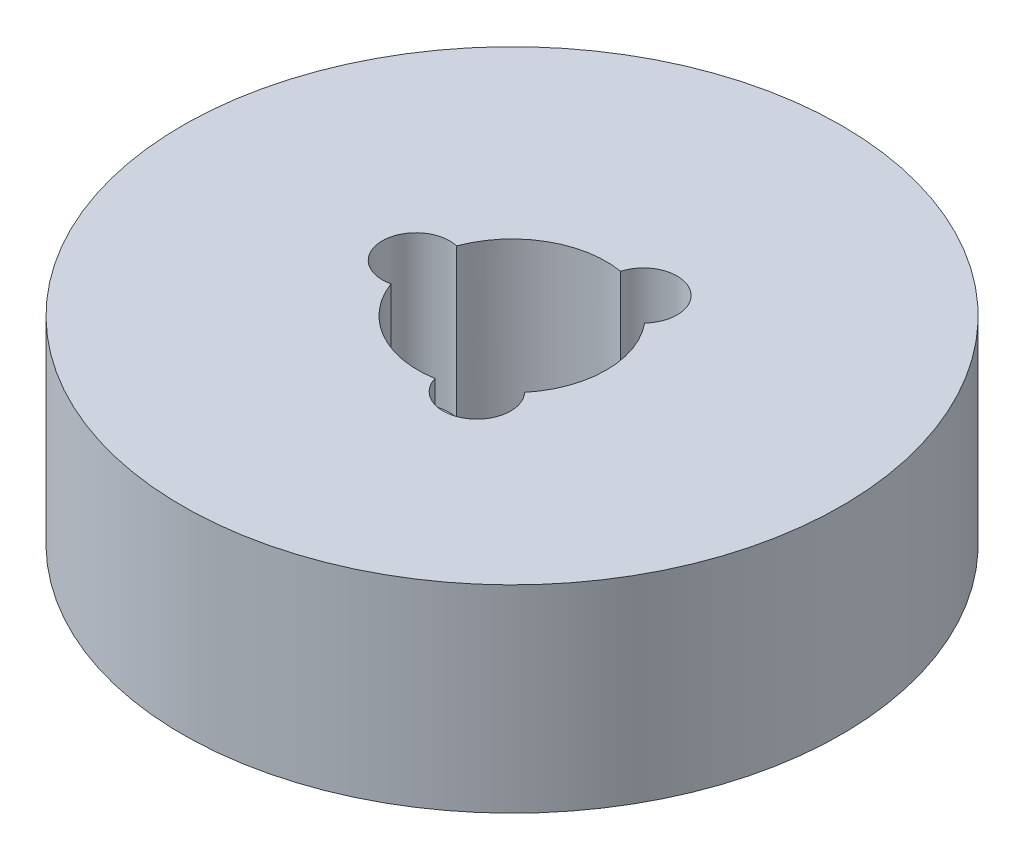
SolidWorks part; units mm, degrees
ref_plane "Front Plane" through (0, 0, 0) normal (0, 0, 1) x (1, 0, 0)
ref_plane "Top Plane" through (0, 0, 0) normal (0, 1, 0) x (1, 0, 0)
ref_plane "Right Plane" through (0, 0, 0) normal (1, 0, 0) x (0, 0, -1)
sketch "Sketch1" plane through (0, 0, 0) normal (0, 1, 0) x (1, 0, 0)
  circle A0 centre (0, 0) radius 35
  dimension "FLANGE_OD" = 70
extrude "Boss-Extrude1" add sketch "Sketch1" along normal blind 21
sketch "Sketch2" plane through (0, 0, 0) normal (0, 1, 0) x (1, 0, 0)
  circle A0 centre (0, 0) radius 10
  dimension "BORE_D" = 20
extrude "Cut-Extrude1" cut sketch "Sketch2" along normal through all
sketch "Sketch3" plane through (0, 21, 0) normal (0, 1, 0) x (1, 0, 0)
  circle A0 centre (0, 0) radius 10.2073 construction
  circle A1 centre (-10.2073, 0) radius 3.5864
  dimension "BOLT_D" = 7.1727
  dimension "BOLT_PCD" = 20.4147
extrude "Cut-Extrude2" cut sketch "Sketch3" against normal blind 15.7974
pattern_circular "CirPattern1" count 3 over 360 about axis through (0, 0, 0) along (0, 1, 0) of "Cut-Extrude2"
